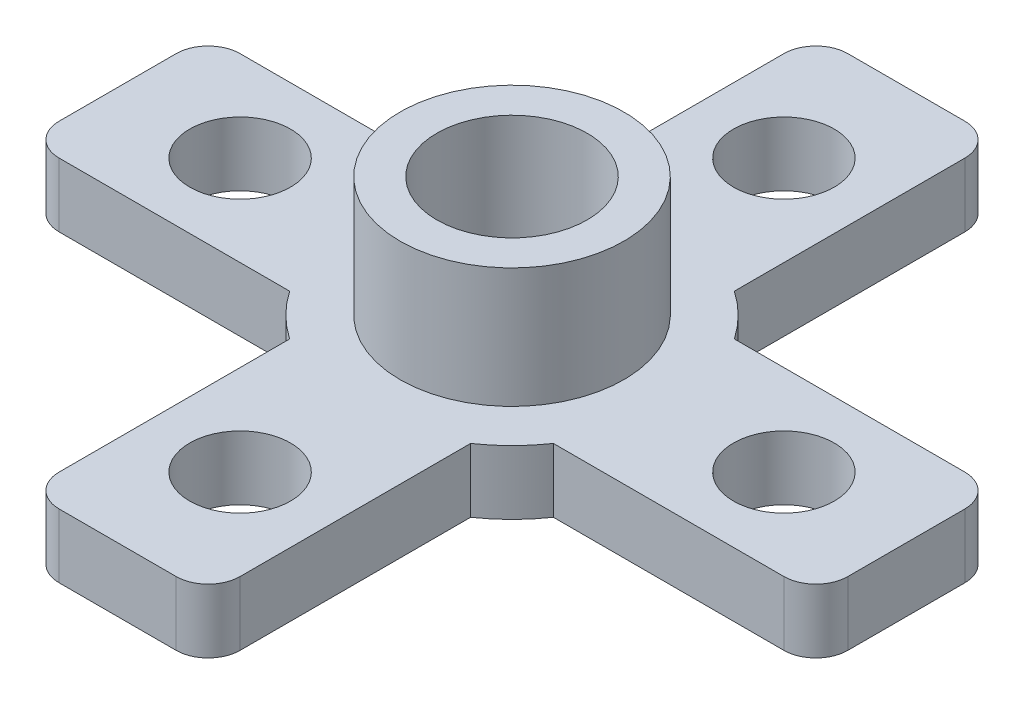
SolidWorks part; units mm, degrees
note: The reader was unsure of these and kept them because the rebuilt part matched: shared geometry of "Sketch1<3>", "Sketch1<4>".
ref_plane "Front Plane" through (0, 0, 0) normal (0, 0, 1) x (1, 0, 0)
ref_plane "Top Plane" through (0, 0, 0) normal (0, 1, 0) x (1, 0, 0)
ref_plane "Right Plane" through (0, 0, 0) normal (1, 0, 0) x (0, 0, -1)
sketch "Sketch1" plane through (0, 0, 0) normal (0, 1, 0) x (1, 0, 0)
  line L0 (2.8284, 2.8284) -> (12.3284, 2.8284)
  line L1 (-2.8284, 2.8284) -> (2.8284, -2.8284)
  line L2 (12.3284, 2.8284) -> (12.3284, -2.8284)
  line L3 (-2.8284, -2.8284) -> (2.8284, 2.8284)
  line L4 (-2.8284, 2.8284) -> (-2.8284, 12.3284)
  line L5 (-2.8284, 12.3284) -> (2.8284, 12.3284)
  line L6 (2.8284, 12.3284) -> (2.8284, 2.8284)
  line L7 (0, 0) -> (0, 8.5)
  line L8 (12.3284, -2.8284) -> (2.8284, -2.8284)
  line L9 (2.8284, -2.8284) -> (2.8284, -12.3284)
  line L10 (2.8284, -12.3284) -> (-2.8284, -12.3284)
  line L11 (-2.8284, -12.3284) -> (-2.8284, -2.8284)
  line L12 (-2.8284, -2.8284) -> (-12.3284, -2.8284)
  line L13 (-12.3284, -2.8284) -> (-12.3284, 2.8284)
  line L14 (-12.3284, 2.8284) -> (-2.8284, 2.8284)
  circle A0 centre (0, 0) radius 2.35
  circle A1 centre (0, 0) radius 4
  circle A2 centre (0, 8.5) radius 1.575
  circle A3 centre (8.5, 0) radius 1.575
  circle A4 centre (0, -8.5) radius 1.575
  circle A5 centre (-8.5, 0) radius 1.575
  circle A6 centre (0, 0) radius 3.5
  circle A7 centre (0, 0) radius 5
  circle A8 centre (0, 0) radius 1.125
  circle A9 centre (0, 0) radius 3
  point P33 (0, 0)
  dimension "D1" = 8
  dimension "D2" = 4.7
  dimension "D5" = 3.15
  dimension "D7" = 7
  dimension "D8" = 10
  dimension "D9" = 2.25
  dimension "D10" = 6
  dimension "D3" = 9.5
  dimension "D4" = 8.5
  dimension "D6" = 4
extrude "Boss-Extrude1" add sketch "Sketch1" along normal blind 2
extrude "Boss-Extrude2" add sketch "Sketch1<3>" along normal blind 5.75 contours L3 A6 L1 A0 | L1 A6 L3 A0 | L7 A6 L1 A0 | L3 A6 L7 A0 | L1 A6 L3 A0 | A9 L7 A6 L1 | A9 L3 A6 L7 | A9 L1 A6 L3 | A9 L3 A6 L1 | A9 L1 A6 L3
sketch "Sketch1<3>" plane through (0, 0, 0) normal (0, 1, 0) x (1, 0, 0) same geometry as "Sketch1"
fillet "Fillet1" radius 1 8 edges at (2.8284, 1, -12.3284) (12.3284, 1, -2.8284) (-2.8284, 1, -12.3284) (-12.3284, 1, -2.8284) (-12.3284, 1, 2.8284) (12.3284, 1, 2.8284) (2.8284, 1, 12.3284) (-2.8284, 1, 12.3284)
extrude "Cut-Extrude1" cut sketch "Sketch1<4>" along normal blind 1 contours L3 A9 L7 A0 | L1 A9 L3 A0 | A8 L1 A0 L3 | A8 L3 A0 L7 | A8 L7 A0 L1 | A8 L3 A0 L1 | A8 L1 A0 L3 | L1 A9 L3 A0 | L7 A9 L1 A0 | L3 A9 L1 A0
sketch "Sketch1<4>" plane through (0, 0, 0) normal (0, 1, 0) x (1, 0, 0) same geometry as "Sketch1"
